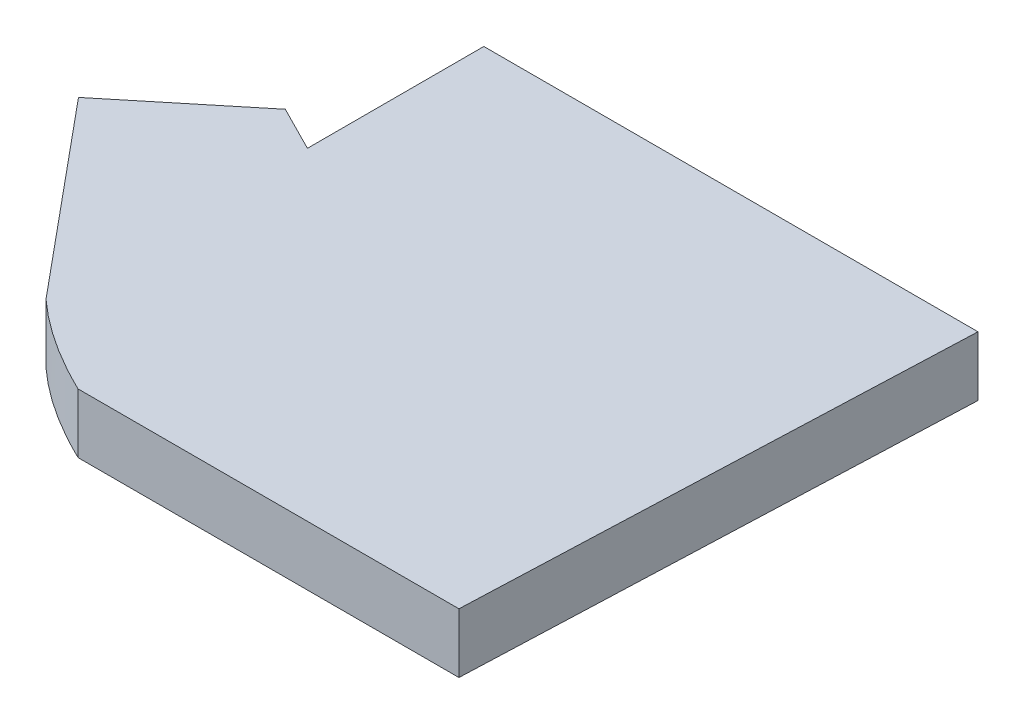
SolidWorks part; units mm, degrees
ref_plane "Front Plane" through (0, 0, 0) normal (0, 0, 1) x (1, 0, 0)
ref_plane "Top Plane" through (0, 0, 0) normal (0, 1, 0) x (1, 0, 0)
ref_plane "Right Plane" through (0, 0, 0) normal (1, 0, 0) x (0, 0, -1)
sketch "Sketch1" plane through (0, 0, 0) normal (0, 1, 0) x (1, 0, 0)
  line L0 (-13.9285, -6.6) -> (69.0715, -6.6)
  line L1 (69.0715, -6.6) -> (65.7758, -90.4854)
  line L3 (65.7758, -90.4854) -> (1.8057, -90.4854)
  line L4 (-13.9285, -6.6) -> (-13.9285, -36.2299)
  line L5 (-40.5595, -48.0529) -> (-13.9285, -80.1379)
  line L6 (-21.4687, -32.4055) -> (-40.5595, -48.0529)
  line L7 (-13.9285, -36.2299) -> (-21.4687, -32.4055)
  line L8 (-38.2991, -55.5466) -> (-20.5101, -40.9662) construction
  line L12 (4.1, -4.6) -> (-4.1, -4.6) construction
  spline S1 degree 2 poles (-13.9285, -80.1379) (-7.5226, -85.9916) (1.8057, -90.4854) knots 0 0 0 1 1 1
  dimension "D1" = 83
  dimension "D2" = 2
extrude "Boss-Extrude1" add sketch "Sketch1" along normal blind 5 and the other way blind 5
sketch "Sketch2" plane through (0, 0, 0) normal (0, 1, 0) x (1, 0, 0)
  line L0 (-14.2796, 7.52) -> (68.7204, 7.52) construction
  line L1 (68.7204, 7.52) -> (73.7519, -16.6643) construction
  line L2 (73.7519, -16.6643) -> (65.2934, -89.2127) construction
  line L3 (65.2934, -89.2127) -> (-4.0312, -89.2127) construction
  line L4 (-4.0312, -89.2127) -> (-18.009, -25.4526) construction
  line L5 (-18.009, -25.4526) -> (-14.2796, 7.52) construction
  line L6 (-4.0312, -89.2127) -> (-4.0312, 7.52) construction
  line L7 (-4.0312, -89.2127) -> (-38.2991, -57.5766) construction
  line L8 (-38.2991, -57.5766) -> (-22.539, -28.3815) construction
  line L9 (-22.539, -28.3815) -> (-18.009, -25.4526) construction
  line L10 (15.6973, 7.52) -> (15.6973, -89.2127) construction
  line L11 (37.0653, 7.52) -> (37.0653, -89.2127) construction
  line L12 (60.2527, 7.52) -> (60.2527, -89.2127) construction
  line L13 (73.3684, -14.8208) -> (-16.8065, -14.8208) construction
  line L14 (-13.4365, -46.3102) -> (70.2954, -46.3102) construction
  dimension "D1" = 83
ref_plane "Plane1" through (0, 0, -7.52) normal (0, 0, 1) x (1, 0, 0)
ref_plane "Plane2" through (0, 0, 89.2127) normal (0, 0, -1) x (-1, 0, 0)
